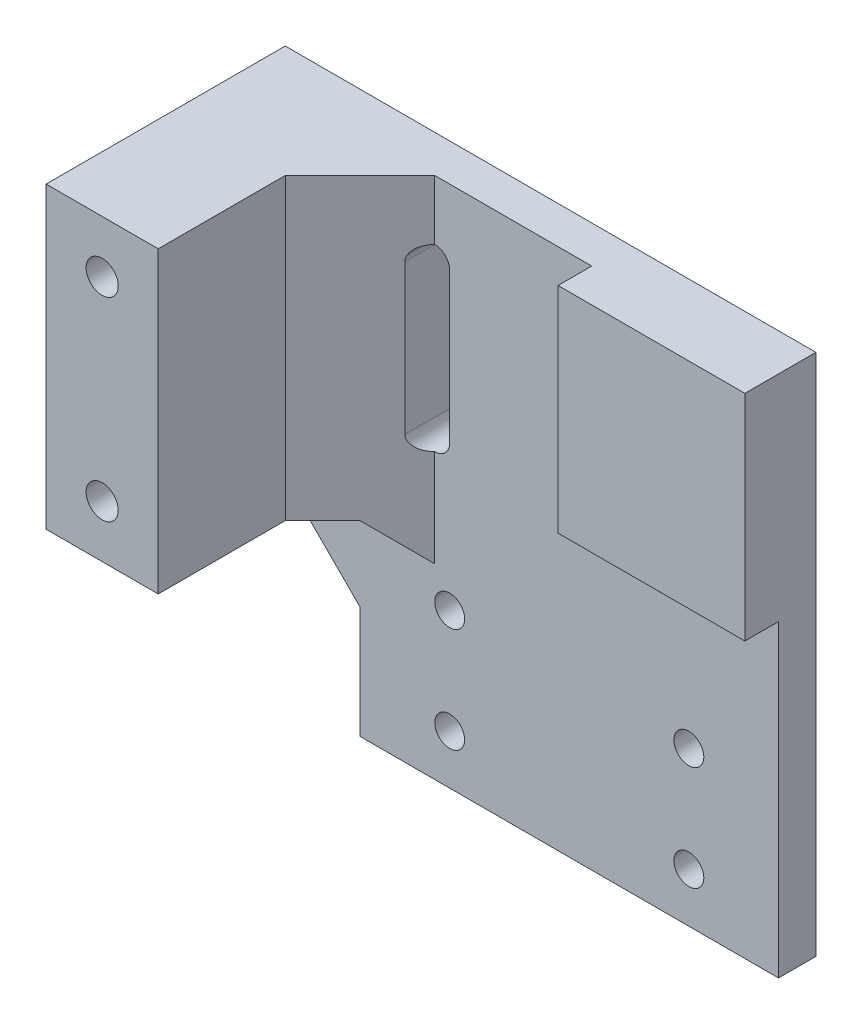
SolidWorks part; units mm, degrees
ref_plane "前视基准面" through (0, 0, 0) normal (0, 0, 1) x (1, 0, 0)
ref_plane "上视基准面" through (0, 0, 0) normal (0, 1, 0) x (1, 0, 0)
ref_plane "右视基准面" through (0, 0, 0) normal (1, 0, 0) x (0, 0, -1)
other "Configuration Table"
sketch "草图1" plane through (0, 0, 0) normal (0, 0, 1) x (1, 0, 0)
  line L1 (-28, -35) -> (28, -35)
  line L2 (-28, -35) -> (-28, 35)
  line L3 (-28, 35) -> (28, 35)
  line L4 (28, -35) -> (28, 35)
  line L5 (-28, -35) -> (28, 35) construction
  line L6 (-28, 35) -> (28, -35) construction
  point P0 (0, 0)
  dimension "D1" = 56
  dimension "D2" = 70
extrude "凸台-拉伸1" add sketch "草图1" along normal blind 5
sketch "草图2" plane through (0, 0, 5) normal (0, 0, 1) x (1, 0, 0)
  line L0 (-16, -28.4) -> (-16, -14.4) construction
  line L1 (-28, -35) -> (28, -35) construction
  line L2 (-28, 35) -> (-28, -35) construction
  circle A0 centre (-16, -28.4) radius 2
  circle A1 centre (-16, -14.4) radius 2
  dimension "D3" = 4
  dimension "D1" = 14
  dimension "D2" = 6.6
  dimension "D4" = 12
extrude "切除-拉伸1" cut sketch "草图2" against normal blind 5
mirror "镜向1" about plane through (0, 0, 0) normal (1, 0, 0) of "切除-拉伸1"
sketch "草图5" plane through (0, 0, 5) normal (0, 0, 1) x (1, 0, 0)
  line L0 (28, 35) -> (-28, 35) construction
  line L1 (3, 35) -> (28, 35)
  line L2 (3, 35) -> (3, 6.3)
  line L3 (3, 6.3) -> (28, 6.3)
  line L4 (28, 35) -> (28, 6.3)
  point P4 (-28, 30)
  point P7 (0, 0)
  point P8 (28, 30)
  point P10 (-28, 30)
  dimension "D1" = 28.7
  dimension "D2" = 25
extrude "凸台-拉伸3" add sketch "草图5" along normal blind 4.5
sketch "草图6" plane through (-28, 0, 0) normal (-1, 0, 0) x (0, 0, 1)
  line L1 (0, 35) -> (0, -35) construction
  line L6 (0, -5) -> (0, 35)
  line L8 (0, -5) -> (32, -5)
  line L9 (32, -5) -> (32, 35)
  line L10 (32, 35) -> (0, 35)
  point P0 (0, 35)
  dimension "D2" = 40
  dimension "D3" = 32
extrude "凸台-拉伸4" add sketch "草图6" along normal blind 15
sketch "草图9" plane through (0, 0, 32) normal (0, 0, 1) x (1, 0, 0)
  line L0 (-43, 15) -> (-28, 15) construction
  line L1 (-43, -5) -> (-43, 35) construction
  line L3 (-35.5, 15) -> (-35.5, 28) construction
  line L5 (-28, -5) -> (-28, 35) construction
  circle A0 centre (-35.5, 28) radius 2.15
  circle A1 centre (-35.5, 2) radius 2.15
  point P4 (-28, 16.5)
  point P13 (-35.5, 8.2333)
  dimension "D1" = 4.3
  dimension "D2" = 26
extrude "切除-拉伸2" cut sketch "草图9" against normal blind 10
sketch "草图10" plane through (0, 0, 5) normal (0, 0, 1) x (1, 0, 0)
  line L0 (-18, 5) -> (-18, 25) construction
  line L1 (-20, 5) -> (-20, 25)
  line L2 (-16, 5) -> (-16, 25)
  line L3 (-28, -5) -> (-28, 35) construction
  line L4 (3, 35) -> (-28, 35) construction
  arc A0 (-20, 5) -> (-16, 5) centre (-18, 5) ccw
  arc A1 (-16, 25) -> (-20, 25) centre (-18, 25) ccw
  point P2 (-18, 15)
  dimension "D1" = 2
  dimension "D2" = 20
  dimension "D3" = 10
  dimension "D4" = 10
extrude "切除-拉伸3" cut sketch "草图10" against normal blind 10
chamfer "倒角1" distance 10 angle 45 1 edges at (-28, 15, 5)
chamfer "倒角2" distance 15 angle 45 1 edges at (-28, -5, 2.5)
chamfer "倒角3" distance 5 angle 45 1 edges at (-30.5, -5, 5)
